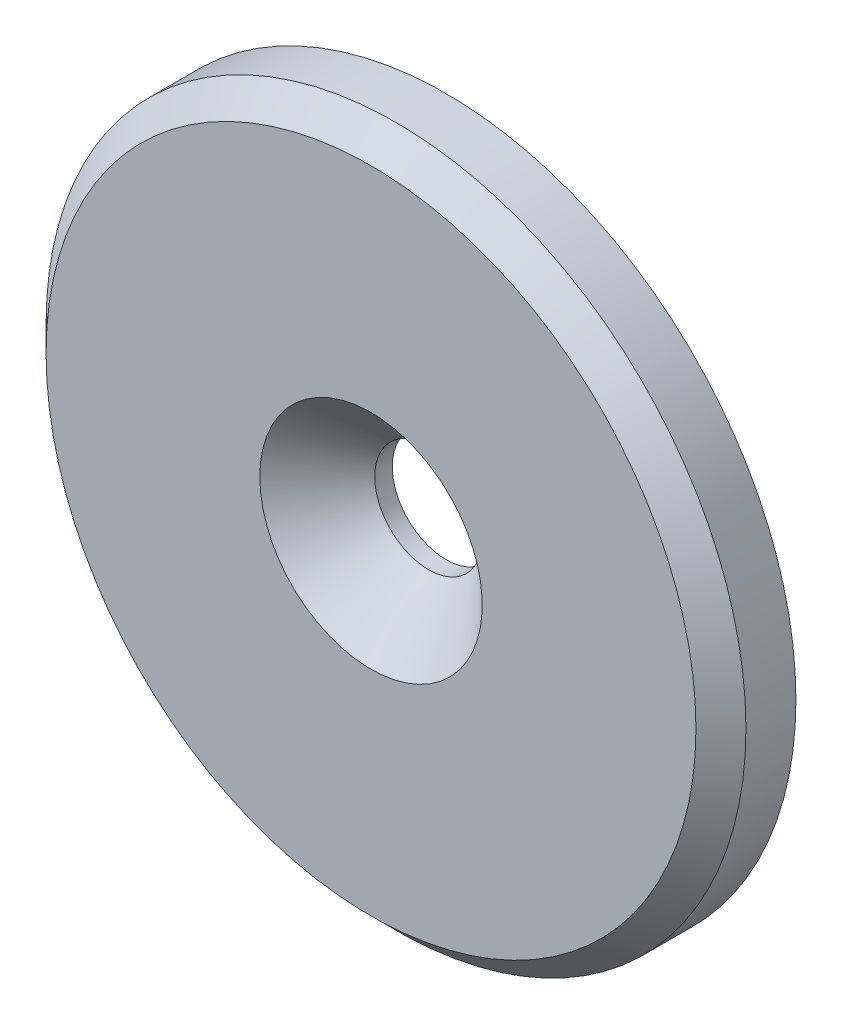
SolidWorks part; units mm, degrees
note: '?' marks a value the reader was unsure of.
ref_plane "Płaszczyzna przednia" through (0, 0, 0) normal (0, 0, 1) x (1, 0, 0)
ref_plane "Płaszczyzna górna" through (0, 0, 0) normal (0, 1, 0) x (1, 0, 0)
ref_plane "Płaszczyzna prawa" through (0, 0, 0) normal (1, 0, 0) x (0, 0, -1)
sketch "Szkic1" plane through (0, 0, 0) normal (0, 1, 0) x (1, 0, 0)
  line L0 (0, 0) -> (14, 0)
  line L1 (14, 0) -> (14, -3)
  line L2 (14, -3) -> (0, -3)
  line L3 (0, -3) -> (0, 0)
  line L4 (0, -3) -> (0, 0) construction
sketch "Szkic2" plane through (0, 0, 0) normal (0, 1, 0) x (1, 0, 0)
  line L0 (13, -3) -> (14, -3)
  line L1 (14, -3) -> (14, -2)
  line L2 (14, -2) -> (13, -3)
  line L3 (0, -3) -> (0, 0) construction
sketch "Szkic3" plane through (0, 0, 0) normal (0, 1, 0) x (1, 0, 0)
  line L0 (0, 0) -> (2.15, 0)
  line L1 (2.15, 0) -> (2.15, -0.7)
  line L2 (2.15, -0.7) -> (4.45, -3)
  line L3 (4.45, -3) -> (0, -3)
  line L4 (0, -3) -> (0, 0)
  line L5 (0, -3) -> (0, 0) construction
revolve "Obrót1" add sketch "Szkic1" angle 360 about L4
revolve "Wycięcie-obrót1" cut sketch "Szkic2" angle 360 about L3
revolve "Wycięcie-obrót2" cut sketch "Szkic3" angle 360 about L5
ref_plane "Płaszczyzna1" through (0, 0, 3) normal (0, 0, 1) x (1, 0, 0)
ref_plane "IP1 XY" through (0, 0, 3) normal (0, 0, 1) x (1, 0, 0)
ref_plane "IP1 XZ" through (0, 0, 0) normal (0, -1, 0) x (-1, 0, 0)
ref_plane "IP1 YZ" through (0, 0, 0) normal (1, 0, 0) x (0, 0, -1)
ref_axis "IP1 X" through (-80.9, 0, 3) along (1, 0, 0)?
ref_axis "IP1 Y" through (0, -50, 3) along (0, 1, 0)?
ref_axis "IP1 Z" through (0, 0, 80.9) along (0, 0, -1)?
sketch3d "IP1"
  point P0 (0, 0, 3)
ref_plane "IP2 XY" through (0, 0, 0) normal (0, 0, 1) x (1, 0, 0)
ref_plane "IP2 XZ" through (0, 0, 0) normal (0, -1, 0) x (-1, 0, 0)
ref_plane "IP2 YZ" through (0, 0, 0) normal (1, 0, 0) x (0, 0, -1)
ref_axis "IP2 X" through (-80.9, 0, 0) along (1, 0, 0)?
ref_axis "IP2 Y" through (0, -50, 0) along (0, 1, 0)?
ref_axis "IP2 Z" through (0, 0, 80.9) along (0, 0, -1)?
sketch3d "IP2"
  point P0 (0, 0, 0)
sketch "Szkic4" plane through (0, 0, 0) normal (1, 0, 0) x (0, 0, -1)
  circle A0 centre (0, 0) radius 10.5
extrude "Dodanie-wyciągnięcie1" add sketch "Szkic4" along normal blind 7 separate body
other "Usuń ścianę1" face at (7, 0, -10.5)
